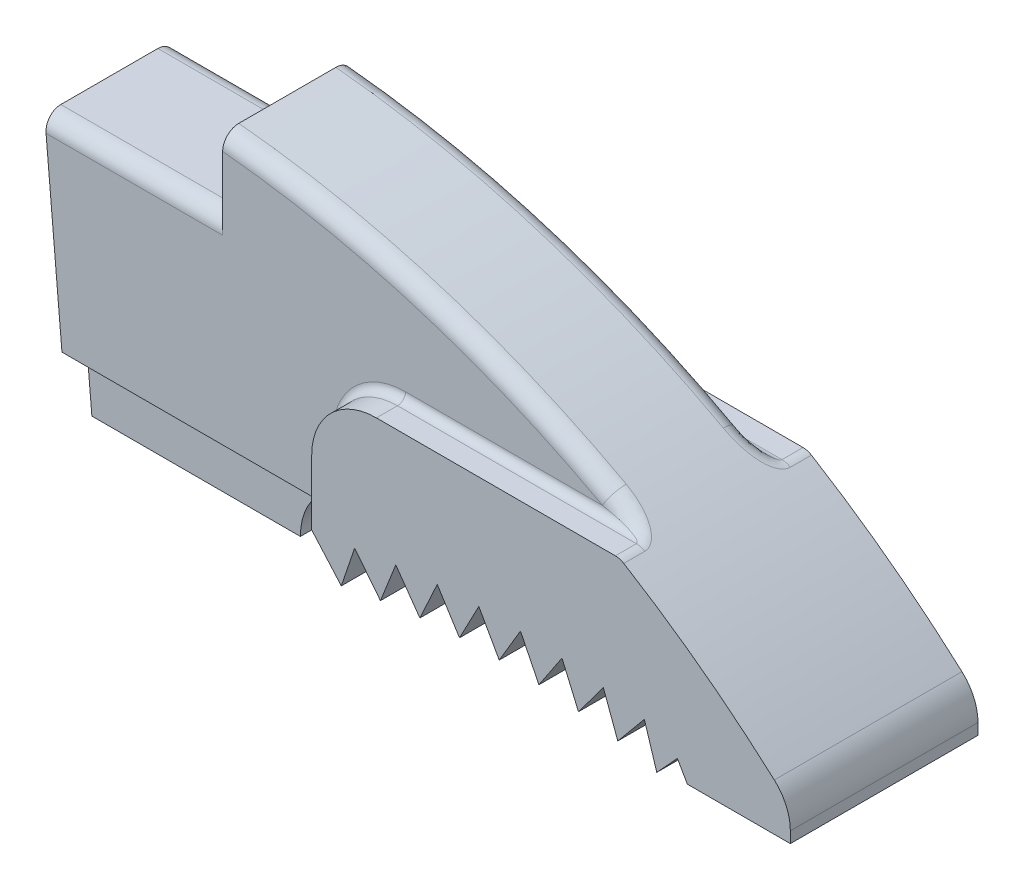
SolidWorks part; units mm, degrees
ref_plane "Front Plane" through (0, 0, 0) normal (0, 0, 1) x (1, 0, 0)
ref_plane "Top Plane" through (0, 0, 0) normal (0, 1, 0) x (1, 0, 0)
ref_plane "Right Plane" through (0, 0, 0) normal (1, 0, 0) x (0, 0, -1)
other "Configuration Table"
sketch "Sketch1" plane through (0, 0, 0) normal (0, 0, 1) x (1, 0, 0)
  line L0 (0, 0) -> (0, 50.8039) construction
  line L1 (0, 0) -> (47.4869, 47.4869) construction
  line L2 (0, 0) -> (-4.2741, 48.8536) construction
  line L3 (-24.9861, 25.7175) -> (66.7901, 25.7175) construction
  line L4 (-3.459, 39.5365) -> (-2.25, 25.7175)
  line L5 (-2.25, 25.7175) -> (5.8796, 25.7175)
  line L6 (5.8796, 25.7175) -> (5.8796, 26.3525)
  line L7 (8.4196, 28.8925) -> (27.2088, 28.8925)
  circle A0 centre (0, 0) radius 39.6875 construction
  arc A1 (27.2088, 28.8925) -> (-3.459, 39.5365) centre (0, 0) ccw
  arc A2 (8.4196, 28.8925) -> (5.8796, 26.3525) centre (8.4196, 26.3525) ccw
  point P16 (5.8796, 28.8925)
  dimension "D1" = 79.375
  dimension "D4" = 13.97
  dimension "D8" = 2.54
  dimension "D2" = 45
  dimension "D3" = 5
  dimension "D5" = 5.8796
  dimension "D6" = 3.175
  dimension "D7" = 21.3292
extrude "Extrude1" add sketch "Sketch1" along normal mid plane 3.175
sketch "Sketch2" plane through (0, 0, 0) normal (0, 0, 1) x (1, 0, 0)
  line L0 (8.4196, 28.8925) -> (-2.5278, 28.8925)
  line L4 (-3.459, 39.5365) -> (-2.25, 25.7175)
  line L5 (-2.25, 25.7175) -> (5.8796, 25.7175)
  line L6 (5.8796, 25.7175) -> (5.8796, 26.3525)
  line L7 (8.4196, 28.8925) -> (27.2088, 28.8925)
  line L8 (-3.459, 39.5365) -> (-2.5278, 28.8925)
  line L11 (8.4196, 28.8925) -> (27.2088, 28.8925)
  arc A2 (27.2088, 28.8925) -> (-3.459, 39.5365) centre (0, 0) ccw
  arc A3 (8.4196, 28.8925) -> (5.8796, 26.3525) centre (8.4196, 26.3525) ccw
  arc A4 (27.2088, 28.8925) -> (-3.459, 39.5365) centre (0, 0) ccw
  dimension "D1" = 0
extrude "Extrude2" add sketch "Sketch2" along normal mid plane 5.08
sketch "Sketch3" plane through (0, 0, 0) normal (0, 0, 1) x (1, 0, 0)
  line L2 (27.2088, 28.8925) -> (8.4196, 28.8925)
  line L4 (20.5175, 33.9725) -> (8.4196, 33.9725)
  line L5 (8.4196, 28.8925) -> (8.4196, 33.9725)
  arc A0 (27.2088, 28.8925) -> (-3.459, 39.5365) centre (0, 0) ccw construction
  arc A1 (27.2088, 28.8925) -> (20.5175, 33.9725) centre (0, 0) ccw
  dimension "D1" = 5.08
extrude "Extrude3" add sketch "Sketch3" along normal mid plane 7.366
sketch "Sketch7" plane through (0, 0, 3.683) normal (0, 0, 1) x (1, 0, 0)
  line L0 (8.4196, 28.8925) -> (27.2088, 28.8925) construction
  line L1 (8.4196, 28.8925) -> (22.4336, 28.8925)
  arc A0 (8.4196, 28.8925) -> (22.4336, 28.8925) centre (15.4266, -1.6318) cw
  dimension "D1" = 31.3182
  dimension "D2" = 4.7752
extrude "Cut-Extrude1" cut sketch "Sketch7" against normal through all
sketch "Sketch4" plane through (0, 0, 0) normal (0, 0, 1) x (1, 0, 0)
  line L0 (8.4196, 28.8925) -> (9.5815, 27.5708)
  line L1 (9.5815, 27.5708) -> (10.1451, 29.2379)
  line L3 (9.5815, 27.5708) -> (9.2893, 29.0307) construction
  line L5 (8.4196, 33.9725) -> (8.4196, 28.8925) construction
  arc A1 (22.4336, 28.8925) -> (8.4196, 28.8925) centre (15.4266, -1.6318) ccw construction
  arc A2 (10.1451, 29.2379) -> (8.4196, 28.8925) centre (15.4266, -1.6318) ccw
  dimension "D1" = 30
  dimension "D2" = 30
  dimension "D4" = 1.7598
extrude "Extrude4" add sketch "Sketch4" along normal up to surface and the other way up to surface up to face at (17.4268, 31.1188, 3.683) other way up to face at (17.4268, 31.1188, -3.683)
ref_axis "Axis1" through (15.4266, -1.6318, 3.683) along (0, 0, -1)
pattern_circular "CirPattern1" count 9 every 3 about axis through (15.4266, -1.6318, 3.683) along (0, 0, -1) of "Extrude4"
sketch "Sketch10" plane through (0, 0, 2.54) normal (0, 0, 1) x (1, 0, 0)
  line L1 (-7.2341, 44.5224) -> (3.7813, 44.5224)
  line L2 (-7.2341, 44.5224) -> (-7.2341, 36.6535)
  line L3 (-7.2341, 36.6535) -> (3.7813, 36.6535)
  line L4 (3.7813, 44.5224) -> (3.7813, 36.6535)
extrude "Cut-Extrude4" cut sketch "Sketch10" against normal through all
fillet "Fillet5" radius 2.54 2 edges at (8.4196, 33.9725, -3.1115) (8.4196, 33.9725, 3.1115)
fillet "Fillet4" radius 0.3175 6 edges at (15.7385, 33.9725, 2.54) (8.4196, 30.1625, 2.54) (8.4196, 30.1625, -2.54) (15.7385, 33.9725, -2.54) (9.1635, 33.2286, -2.54) (9.1635, 33.2286, 2.54)
fillet "Fillet6" radius 0.635 10 edges at (20.5175, 33.9725, 3.2702) (20.4507, 34.0128, 2.7028) (12.1648, 37.7772, 2.54) (20.5175, 33.9725, -3.2702) (20.4783, 33.9961, -2.7373) (2.9459, 28.8925, -1.5875) (2.9459, 28.8925, 1.5875) (12.1648, 37.7772, -2.54) (0.2873, 36.6535, -2.54) (0.2873, 36.6535, 2.54)
sketch "Sketch5" plane through (0, 28.8925, 0) normal (0, -1, 0) x (1, 0, 0)
  line L4 (22.4336, 3.683) -> (22.4336, -3.683)
  line L5 (22.4336, -3.683) -> (27.2088, -3.683)
  line L6 (27.2088, -3.683) -> (27.2088, 3.683)
  line L7 (27.2088, 3.683) -> (22.4336, 3.683)
  line L8 (22.4336, 3.683) -> (22.4336, -3.683)
  line L9 (22.4336, -3.683) -> (27.2088, -3.683)
  line L10 (27.2088, -3.683) -> (27.2088, 3.683)
  line L11 (27.2088, 3.683) -> (22.4336, 3.683)
  dimension "D1" = 0
extrude "Extrude5" add sketch "Sketch5" along normal blind 1.27
chamfer "Chamfer1" distance 1.27 angle 30 1 edges at (22.4336, 27.6225, 0) first distance on face at (22.4336, 27.7774, 0)
fillet "Fillet7" radius 1.905 1 edges at (27.2088, 28.8925, 0)
sketch "Sketch9" plane through (5.8796, 0, 0) normal (1, 0, 0) x (0, 0, -1)
  line L4 (1.5875, 25.7175) -> (1.5875, 26.3525)
  line L5 (1.5875, 26.3525) -> (-1.5875, 26.3525)
  line L6 (-1.5875, 26.3525) -> (-1.5875, 25.7175)
  line L7 (-1.5875, 25.7175) -> (1.5875, 25.7175)
  line L8 (1.5875, 25.7175) -> (1.5875, 26.3525)
  line L9 (1.5875, 26.3525) -> (-1.5875, 26.3525)
  line L10 (-1.5875, 26.3525) -> (-1.5875, 25.7175)
  line L11 (-1.5875, 25.7175) -> (1.5875, 25.7175)
  dimension "D1" = 0
extrude "Cut-Extrude3" cut sketch "Sketch9" against normal through all
